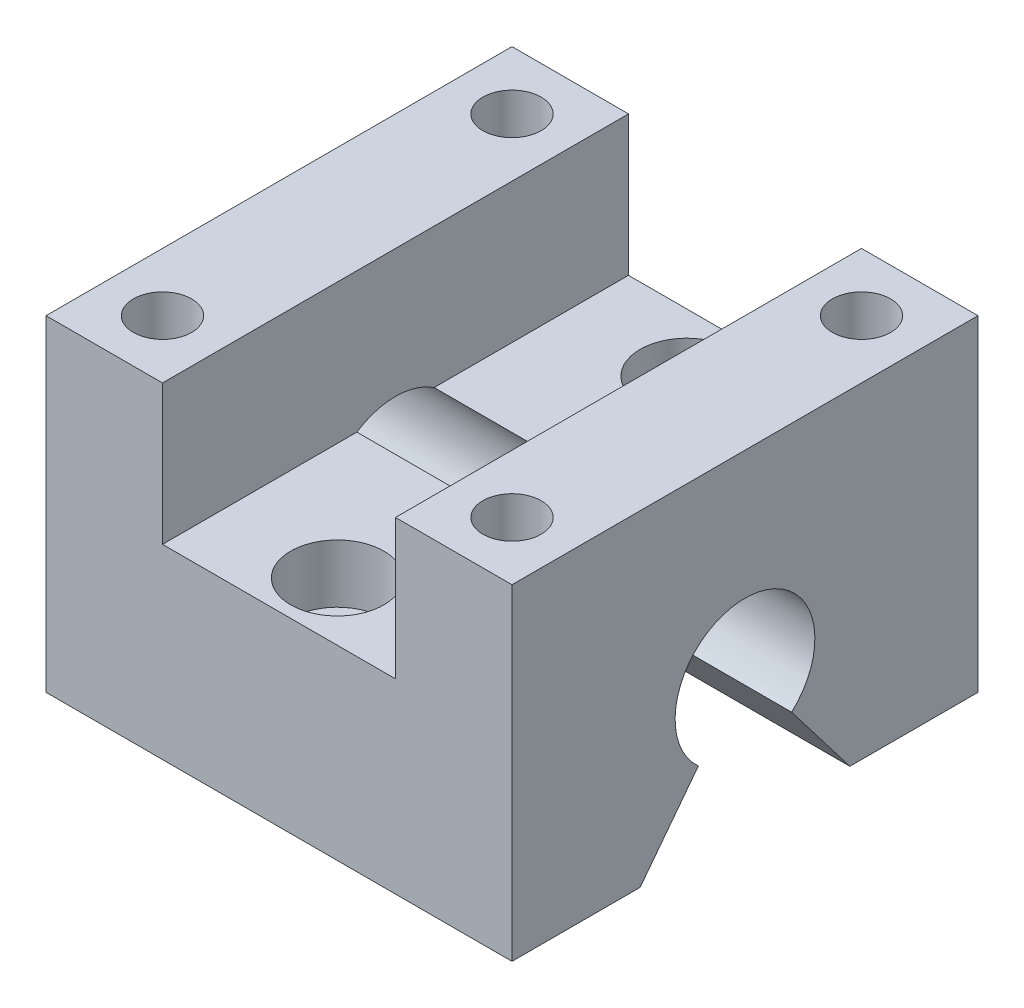
SolidWorks part; units mm, degrees
ref_plane "Спереди" through (0, 0, 0) normal (0, 0, 1) x (1, 0, 0)
ref_plane "Сверху" through (0, 0, 0) normal (0, 1, 0) x (1, 0, 0)
ref_plane "Справа" through (0, 0, 0) normal (1, 0, 0) x (0, 0, -1)
sketch "Эскиз1" plane through (0, 0, 0) normal (1, 0, 0) x (0, 0, -1)
  line L0 (-4, -7.4721) -> (-9, -14)
  line L1 (-20, -14) -> (-9, -14)
  line L2 (-20, -14) -> (-20, 14)
  line L3 (-20, 14) -> (20, 14)
  line L4 (20, -14) -> (20, 14)
  line L5 (0, 14) -> (0, -14) construction
  line L6 (-20, 0) -> (20, 0) construction
  line L11 (4, -7.4721) -> (9, -14)
  line L12 (9, -14) -> (20, -14)
  arc A1 (4, -7.4721) -> (-4, -7.4721) centre (0, -3) ccw
  point P0 (0, 0)
  point P5 (0, 0)
  dimension "D3" = 12
  dimension "D1" = 28
  dimension "D2" = 40
  dimension "D4" = 11
  dimension "D5" = 8
  dimension "D6" = 18
extrude "Бобышка-Вытянуть1" add sketch "Эскиз1" along normal mid plane 40
sketch "Эскиз2" plane through (0, 0, 0) normal (0, 0, 1) x (1, 0, 0)
  line L0 (0, 0) -> (0, 16.3424) construction
  line L1 (-10, 21.6164) -> (10, 21.6164)
  line L2 (-10, 21.6164) -> (-10, 2)
  line L3 (-10, 2) -> (10, 2)
  line L4 (10, 21.6164) -> (10, 2)
  line L5 (20, 14) -> (-20, 14) construction
  point P7 (0, 0)
  dimension "D1" = 20
  dimension "D2" = 12
extrude "Вырез-Вытянуть1" cut sketch "Эскиз2" against normal through all and the other way through all
sketch "Эскиз3" plane through (0, 2, 0) normal (0, 1, 0) x (1, 0, 0)
  line L0 (0, 0) -> (5.226, 0) construction
  circle A0 centre (0, 15) radius 4
  circle A1 centre (0, -15) radius 4
  point P7 (0, 0)
  point P8 (-4.2389, 15)
  point P9 (0, 0)
  dimension "D1" = 8
  dimension "D2" = 30
extrude "Вырез-Вытянуть2" cut sketch "Эскиз3" against normal blind 5
sketch "Эскиз4" plane through (0, 14, 0) normal (0, 1, 0) x (1, 0, 0)
  line L0 (0, 6.6125) -> (0, 0) construction
  line L1 (0, 0) -> (7.2525, 0) construction
  circle A0 centre (-15, 15) radius 2.5
  circle A1 centre (-15, -15) radius 2.5
  circle A2 centre (15, -15) radius 2.5
  circle A3 centre (15, 15) radius 2.5
  point P12 (0, 0)
  point P13 (0, 0)
  point P14 (0, 0)
  point P15 (0, 0)
  point P16 (0, 0)
  point P17 (0, 0)
  dimension "D1" = 5
  dimension "D2" = 30
  dimension "D3" = 30
extrude "Вырез-Вытянуть3" cut sketch "Эскиз4" against normal blind 10
